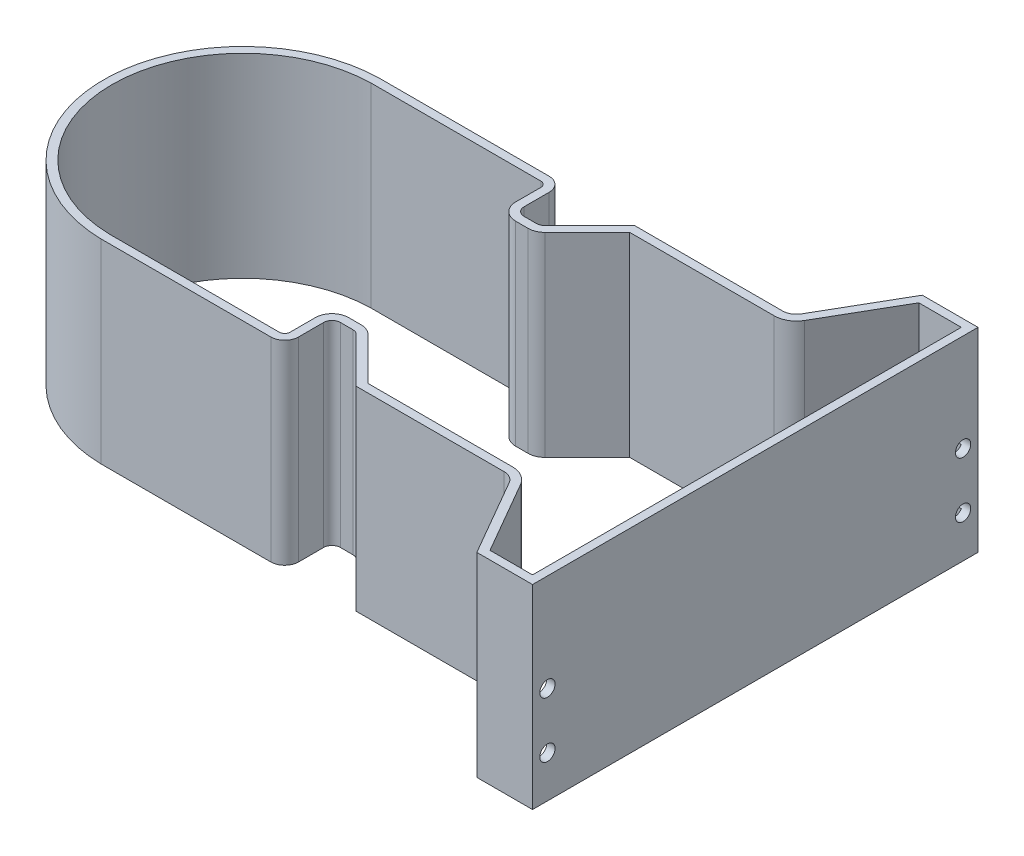
SolidWorks part; units mm, degrees
ref_plane "Front Plane" through (0, 0, 0) normal (0, 0, 1) x (1, 0, 0)
ref_plane "Top Plane" through (0, 0, 0) normal (0, 1, 0) x (1, 0, 0)
ref_plane "Right Plane" through (0, 0, 0) normal (1, 0, 0) x (0, 0, -1)
sketch "Sketch1" plane through (0, 0, 0) normal (0, 1, 0) x (1, 0, 0)
  line L0 (15.2546, 44.9902) -> (15.2546, 35.9902)
  line L1 (-50.7454, -49.9902) -> (10.2546, -49.9902)
  line L3 (-50.7454, 49.9902) -> (10.2546, 49.9902)
  line L5 (-50.7454, -49.9902) -> (50.7454, 49.9902) construction
  line L6 (-50.7454, 49.9902) -> (50.7454, -49.9902) construction
  line L7 (18.2546, 32.9902) -> (22.7119, 32.9902)
  line L8 (24.8333, 33.8689) -> (40.9546, 49.9902)
  line L9 (40.9546, 49.9902) -> (94.0678, 49.9902)
  line L10 (98.398, 52.4902) -> (114.2807, 80)
  line L11 (114.2807, 80) -> (134.2807, 80)
  line L12 (-49.7577, 0) -> (134.2807, 0) construction
  line L13 (134.2807, 80) -> (134.2807, -80)
  line L14 (40.9546, 49.9902) -> (96.9546, 49.9902)
  line L15 (40.9546, 49.9902) -> (50.7454, 49.9902)
  line L17 (114.2807, -80) -> (134.2807, -80)
  line L18 (98.398, -52.4902) -> (114.2807, -80)
  line L19 (40.9546, -49.9902) -> (94.0678, -49.9902)
  line L20 (18.2546, -32.9902) -> (22.7119, -32.9902)
  line L21 (24.8333, -33.8689) -> (40.9546, -49.9902)
  line L22 (15.2546, -44.9902) -> (15.2546, -35.9902)
  line L23 (40.9546, -49.9902) -> (50.7454, -49.9902)
  arc A0 (-50.7454, 49.9902) -> (-50.7454, -49.9902) centre (-49.7577, 0) ccw
  arc A1 (22.7119, 32.9902) -> (24.8333, 33.8689) centre (22.7119, 35.9902) ccw
  arc A2 (18.2546, 32.9902) -> (15.2546, 35.9902) centre (18.2546, 35.9902) cw
  arc A3 (15.2546, 44.9902) -> (10.2546, 49.9902) centre (10.2546, 44.9902) ccw
  arc A4 (15.2546, -44.9902) -> (10.2546, -49.9902) centre (10.2546, -44.9902) cw
  arc A5 (22.7119, -32.9902) -> (24.8333, -33.8689) centre (22.7119, -35.9902) cw
  arc A6 (18.2546, -32.9902) -> (15.2546, -35.9902) centre (18.2546, -35.9902) ccw
  arc A7 (98.398, -52.4902) -> (94.0678, -49.9902) centre (94.0678, -54.9902) ccw
  arc A8 (98.398, 52.4902) -> (94.0678, 49.9902) centre (94.0678, 54.9902) cw
  point P0 (0, 0)
  point P24 (23.9546, 32.9902)
  point P27 (15.2546, 32.9902)
  point P30 (15.2546, 49.9902)
  point P33 (15.2546, -49.9902)
  point P37 (23.9546, -32.9902)
  point P40 (15.2546, -32.9902)
  point P43 (96.9546, -49.9902)
  dimension "D2" = 100
  dimension "D11" = 3
  dimension "D12" = 5
  dimension "D13" = 5
  dimension "D14" = 3
  dimension "D15" = 5
  dimension "D1" = 120
  dimension "D3" = 8.7
  dimension "D4" = 135
  dimension "D5" = 17
  dimension "D6" = 56
  dimension "D7" = 160
  dimension "D8" = 20
  dimension "D10" = 66
extrude "Boss-Extrude1" add sketch "Sketch1" along normal blind 70 contours L3 A0 L1 L13 L11 L10 L14 L9 L8 L7 L0 region at (29.4264, 0, 0)
sketch "Sketch3" plane through (134.2807, 0, 0) normal (1, 0, 0) x (0, 0, -1)
  line L0 (-80, 70) -> (80, 0) construction
  line L1 (-80, 0) -> (80, 70) construction
  line L2 (0, 35) -> (-72.6822, 35) construction
  line L3 (-74.647, 35) -> (-74.647, 15) construction
  line L4 (0, 35) -> (0, 70) construction
  line L5 (80, 70) -> (-80, 70) construction
  line L6 (0, 35) -> (-80, 35) construction
  line L7 (-80, 70) -> (80, 70)
  line L8 (-80, 70) -> (-80, 0)
  line L9 (-80, 0) -> (80, 0)
  line L10 (80, 70) -> (80, 0)
  line L11 (-80, 70) -> (80, 0) construction
  line L12 (-80, 0) -> (80, 70) construction
  line L13 (74.647, 35) -> (74.647, 15) construction
  circle A0 centre (-74.647, 15) radius 2.75
  circle A1 centre (-74.647, 35) radius 2.75
  circle A17 centre (74.647, 35) radius 2.75
  circle A18 centre (74.647, 15) radius 2.75
  dimension "D1" = 20
sketch "Sketch4" plane through (0, 70, 0) normal (0, 1, 0) x (1, 0, 0)
  line L0 (22.7119, 32.9902) -> (22.7119, -32.9902) construction
  line L1 (22.7119, 0) -> (-0.2253, 0) construction
  line L2 (22.7119, 21) -> (13.7119, 21)
  line L3 (10.7119, 18) -> (10.7119, -18)
  line L4 (13.7119, -21) -> (22.7119, -21)
  line L5 (10.7119, 21) -> (22.7119, -21) construction
  line L6 (22.7119, 21) -> (10.7119, -21) construction
  line L7 (22.7119, 21) -> (22.7119, -21)
  arc A0 (13.7119, -21) -> (10.7119, -18) centre (13.7119, -18) cw
  arc A1 (10.7119, 18) -> (13.7119, 21) centre (13.7119, 18) cw
  point P8 (16.7119, 0)
  dimension "D3" = 3
  dimension "D1" = 42
  dimension "D2" = 12
extrude "Cut-Extrude2" cut sketch "Sketch4" against normal through all
sketch "Sketch5" plane through (0, 70, 0) normal (0, 1, 0) x (1, 0, 0)
  line L30 (116.0128, 77) -> (100.996, 50.9902)
  line L31 (94.0678, 46.9902) -> (42.1972, 46.9902)
  line L32 (42.1972, 46.9902) -> (26.9546, 31.7476)
  line L33 (22.7119, 29.9902) -> (18.2546, 29.9902)
  line L34 (12.2546, 35.9902) -> (12.2546, 44.9902)
  line L35 (10.2546, 46.9902) -> (-50.7153, 46.9902)
  line L36 (-50.7153, -46.9902) -> (10.2546, -46.9902)
  line L37 (12.2546, -44.9902) -> (12.2546, -35.9902)
  line L38 (18.2546, -29.9902) -> (22.7119, -29.9902)
  line L39 (26.9546, -31.7476) -> (42.1972, -46.9902)
  line L40 (42.1972, -46.9902) -> (94.0678, -46.9902)
  line L41 (100.996, -50.9902) -> (116.0128, -77)
  line L42 (116.0128, -77) -> (131.2807, -77)
  line L43 (131.2807, -77) -> (131.2807, 77)
  line L44 (131.2807, 77) -> (116.0128, 77)
  line L45 (116.0128, 77) -> (100.996, 50.9902)
  line L46 (94.0678, 46.9902) -> (42.1972, 46.9902)
  line L47 (42.1972, 46.9902) -> (26.9546, 31.7476)
  line L48 (22.7119, 29.9902) -> (18.2546, 29.9902)
  line L49 (12.2546, 35.9902) -> (12.2546, 44.9902)
  line L50 (10.2546, 46.9902) -> (-50.7153, 46.9902)
  line L51 (-50.7153, -46.9902) -> (10.2546, -46.9902)
  line L52 (12.2546, -44.9902) -> (12.2546, -35.9902)
  line L53 (18.2546, -29.9902) -> (22.7119, -29.9902)
  line L54 (26.9546, -31.7476) -> (42.1972, -46.9902)
  line L55 (42.1972, -46.9902) -> (94.0678, -46.9902)
  line L56 (100.996, -50.9902) -> (116.0128, -77)
  line L57 (116.0128, -77) -> (131.2807, -77)
  line L58 (131.2807, -77) -> (131.2807, 77)
  line L59 (131.2807, 77) -> (116.0128, 77)
  arc A18 (94.0678, 46.9902) -> (100.996, 50.9902) centre (94.0678, 54.9902) ccw
  arc A19 (22.7119, 29.9902) -> (26.9546, 31.7476) centre (22.7119, 35.9902) ccw
  arc A20 (12.2546, 35.9902) -> (18.2546, 29.9902) centre (18.2546, 35.9902) ccw
  arc A21 (-50.7153, 46.9902) -> (-50.7153, -46.9902) centre (-49.7577, 0) ccw
  arc A22 (18.2546, -29.9902) -> (12.2546, -35.9902) centre (18.2546, -35.9902) ccw
  arc A23 (26.9546, -31.7476) -> (22.7119, -29.9902) centre (22.7119, -35.9902) ccw
  arc A24 (100.996, -50.9902) -> (94.0678, -46.9902) centre (94.0678, -54.9902) ccw
  arc A25 (94.0678, 46.9902) -> (100.996, 50.9902) centre (94.0678, 54.9902) ccw
  arc A26 (22.7119, 29.9902) -> (26.9546, 31.7476) centre (22.7119, 35.9902) ccw
  arc A27 (12.2546, 35.9902) -> (18.2546, 29.9902) centre (18.2546, 35.9902) ccw
  arc A28 (-50.7153, 46.9902) -> (-50.7153, -46.9902) centre (-49.7577, 0) ccw
  arc A29 (18.2546, -29.9902) -> (12.2546, -35.9902) centre (18.2546, -35.9902) ccw
  arc A30 (26.9546, -31.7476) -> (22.7119, -29.9902) centre (22.7119, -35.9902) ccw
  arc A31 (100.996, -50.9902) -> (94.0678, -46.9902) centre (94.0678, -54.9902) ccw
  arc A32 (12.2546, 44.9902) -> (10.2546, 46.9902) centre (10.2546, 44.9902) ccw
  arc A33 (12.2546, 44.9902) -> (10.2546, 46.9902) centre (10.2546, 44.9902) ccw
  arc A34 (10.2546, -46.9902) -> (12.2546, -44.9902) centre (10.2546, -44.9902) ccw
  arc A35 (10.2546, -46.9902) -> (12.2546, -44.9902) centre (10.2546, -44.9902) ccw
  dimension "D1" = 3
extrude "Cut-Extrude3" cut sketch "Sketch5" against normal blind 70
extrude "Cut-Extrude6" cut sketch "Sketch3" against normal blind 5 contours A1 | A0 | A17 | A18
